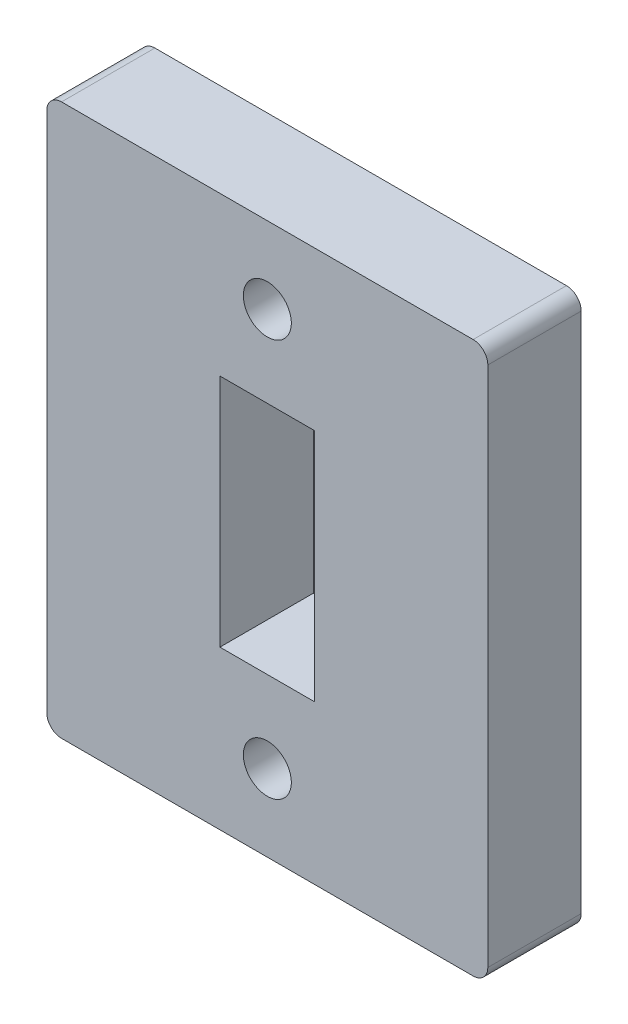
SolidWorks part; units mm, degrees
ref_plane "Front Plane" through (0, 0, 0) normal (0, 0, 1) x (1, 0, 0)
ref_plane "Top Plane" through (0, 0, 0) normal (0, 1, 0) x (1, 0, 0)
ref_plane "Right Plane" through (0, 0, 0) normal (1, 0, 0) x (0, 0, -1)
sketch "Sketch1" plane through (0, 0, 0) normal (0, 0, 1) x (1, 0, 0)
  line L0 (60, -37.5) -> (0, -37.5) construction
  line L1 (0, 0) -> (60, 0)
  line L2 (0, 0) -> (0, -75)
  line L3 (0, -75) -> (60, -75)
  line L4 (60, 0) -> (60, -75)
  line L5 (30, -37.5) -> (30, -21.525) construction
  line L6 (30, -21.525) -> (36.45, -21.525)
  line L7 (36.45, -21.525) -> (36.45, -53.475)
  line L8 (36.45, -53.475) -> (30, -53.475)
  line L9 (30, -53.475) -> (23.55, -53.475)
  line L10 (23.55, -53.475) -> (23.55, -21.525)
  line L11 (23.55, -21.525) -> (30, -21.525)
  line L12 (30, -37.5) -> (30, -53.475) construction
  line L13 (30, 0) -> (30, -13.25) construction
  line L14 (30, -75) -> (30, -64.56) construction
  dimension "D1" = 75
  dimension "D2" = 60
  dimension "D3" = 12.9
  dimension "D4" = 31.95
  dimension "D5" = 13.25
  dimension "D6" = 10.44
extrude "Boss-Extrude1" add sketch "Sketch1" along normal blind 12.7
sketch "Sketch4" plane through (0, 0, 0) normal (0, 0, -1) x (-1, 0, 0)
  line L0 (-30, 0) -> (-30, -10.44)
  line L1 (-60, 0) -> (0, 0) construction
  line L2 (-30, -75) -> (-30, -64.56)
  line L3 (0, -75) -> (-60, -75) construction
  dimension "D1" = 10.44
  dimension "D2" = 10.44
hole_wizard "CSK for 1/4 Flat Head Machine Screw1" positions "Sketch5" profile "Sketch6" countersink size "1/4" standard "ANSI Inch" end condition through all
sketch "Sketch5" plane through (0, 0, 0) normal (0, 0, -1) x (-1, 0, 0)
  point P0 (-30, -10.44)
  point P3 (-30, -64.56)
sketch "Sketch6" plane through (30, -10.44, 0) normal (1, 0, 0) x (0, 1, 0)
  line L0 (0, 0) -> (0, 12.7)
  line L1 (0, 12.7) -> (3.2639, 12.7)
  line L2 (3.2639, 12.7) -> (3.2639, 3.6524)
  line L3 (3.2639, 3.6524) -> (6.4389, 0)
  line L5 (6.4389, 0) -> (0, 0)
  line L6 (-3.2639, 3.6524) -> (-6.4389, 0) construction
  line L11 (0, -6.35) -> (0, 107.95) construction
  dimension "Thru Hole Dia." = 6.5278
  dimension "Thru Hole Depth" = 12.7
  dimension "Near C'Sink Dia." = 12.8778
  dimension "Near C'Sink Angle" = 82
fillet "Fillet1" radius 2 4 edges at (0, 0, 6.35) (60, 0, 6.35) (0, -75, 6.35) (60, -75, 6.35)
